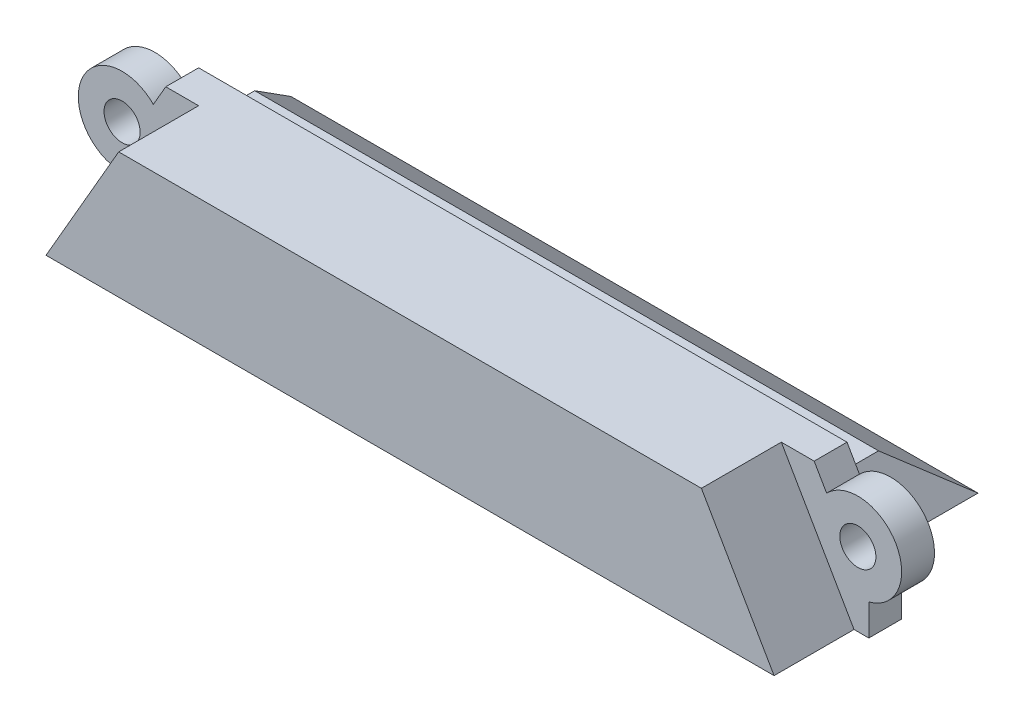
SolidWorks part; units mm, degrees
ref_plane "Front" through (0, 0, 0) normal (0, 0, 1) x (1, 0, 0)
ref_plane "Top" through (0, 0, 0) normal (0, 1, 0) x (1, 0, 0)
ref_plane "Right" through (0, 0, 0) normal (1, 0, 0) x (0, 0, -1)
other "Configuration Table"
sketch "Sketch1" plane through (0, 0, 0) normal (0, 0, 1) x (1, 0, 0)
  line L0 (-33.25, -5.75) -> (33.25, -5.75)
  line L1 (33.25, -5.75) -> (26.6105, 5.75)
  line L2 (26.6105, 5.75) -> (-26.6105, 5.75)
  line L3 (-26.6105, 5.75) -> (-33.25, -5.75)
  line L4 (0, 43.865) -> (0, -48.4441) construction
  line L6 (-28.4869, 2.5) -> (28.4869, 2.5)
  line L8 (31.3736, -2.5) -> (-31.3736, -2.5)
  line L9 (-36.7321, 0) -> (38.2941, 0) construction
  point P13 (-24.9575, 3.6177)
  point P14 (0, 0)
  point P15 (-27.8135, 3.6663)
  point P16 (0, 0)
  point P17 (-31.3314, -3.2427)
  point P18 (27.8697, 3.569)
  point P19 (31.5496, -2.8048)
  point P20 (31.3736, -2.5)
  point P21 (-31.3736, -2.5)
  dimension "D1" = 66.5
  dimension "D2" = 11.5
  dimension "D3" = 60
  dimension "D4" = 5
extrude "Boss-Extrude1" add sketch "Sketch1" against normal blind 10.3 contours L3 L6 L1 L2 | L6 L3 L0 L1 | L1 L8 L3 L0 region at (0, -4.1407, 0) region at (0, -0.0402, 0) region at (0, 4.1066, 0)
extrude "Boss-Extrude2" add sketch "Sketch1<5>" against normal blind 20.5 contours L8 L1 L6 L3 region at (0, -0.0402, 0)
sketch "Sketch1<5>" plane through (0, 0, 0) normal (0, 0, 1) x (1, 0, 0) same geometry as "Sketch1"
sketch "Sketch2" plane through (0, 0, 0) normal (1, 0, 0) x (0, 0, -1)
  line L0 (20.5, -2.5) -> (14.3, 2.5)
  line L1 (20.5, 2.5) -> (10.3, 2.5) construction
  line L2 (14.3, 2.5) -> (20.5, 2.5)
  line L3 (20.5, 2.5) -> (20.5, -2.5)
  dimension "D1" = 4
extrude "Cut-Extrude1" cut sketch "Sketch2" against normal through all both and the other way through all
sketch "Sketch3" plane through (0, 0, -10.3) normal (0, 0, -1) x (-1, 0, 0)
  line L0 (-33.25, -5.75) -> (-34.6, -5.75)
  line L1 (-34.6, -5.75) -> (-34.6, -2.8921)
  line L2 (-30.7459, 3.7834) -> (-29.6105, 5.75)
  line L3 (-29.6105, 5.75) -> (-26.6105, 5.75)
  line L4 (-26.6105, 5.75) -> (26.6105, 5.75) construction
  line L5 (-28.4869, 2.5) -> (-26.6105, 5.75) construction
  line L6 (-33.25, -5.75) -> (-26.6105, 5.75)
  arc A0 (-30.7459, 3.7834) -> (-34.6, -2.8921) centre (-33.6, 0.9809) ccw
  circle A1 centre (-33.6, 0.9809) radius 1.65
  dimension "D2" = 8
  dimension "D5" = 3.3
  dimension "D1" = 1
  dimension "D3" = 1.35
  dimension "D4" = 3
extrude "Boss-Extrude3" add sketch "Sketch3" against normal blind 3
mirror "Mirror1" about plane through (0, 0, 0) normal (1, 0, 0) of "Boss-Extrude3"
